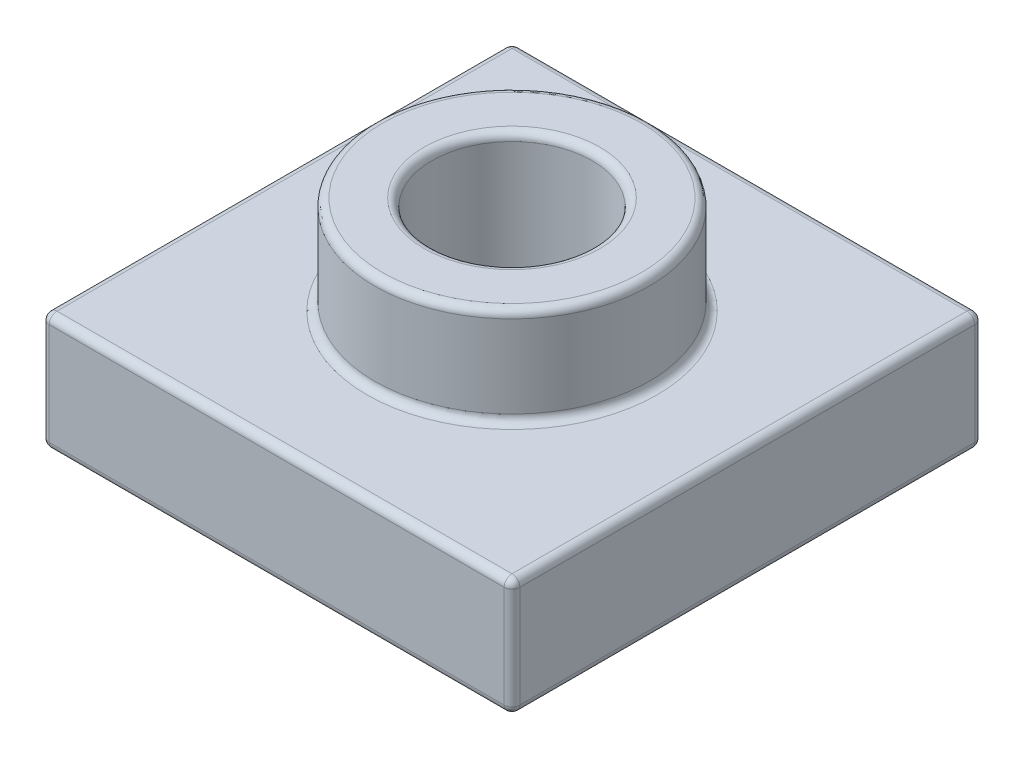
SolidWorks part; units mm, degrees
ref_plane "Front" through (0, 0, 0) normal (0, 0, 1) x (1, 0, 0)
ref_plane "Top" through (0, 0, 0) normal (0, 1, 0) x (1, 0, 0)
ref_plane "Right" through (0, 0, 0) normal (1, 0, 0) x (0, 0, -1)
sketch "Sketch1" plane through (0, 0, 0) normal (0, 1, 0) x (1, 0, 0)
  line L1 (-60, 60) -> (60, 60)
  line L2 (-60, 60) -> (-60, -60)
  line L3 (-60, -60) -> (60, -60)
  line L4 (60, 60) -> (60, -60)
  line L5 (-60, 60) -> (60, -60) construction
  line L6 (-60, -60) -> (60, 60) construction
  point P0 (0, 0)
  dimension "D1" = 120
  dimension "D2" = 120
extrude "Boss-Extrude1" add sketch "Sketch1" along normal blind 30
sketch "Sketch2" plane through (0, 30, 0) normal (0, 1, 0) x (1, 0, 0)
  circle A0 centre (0, 0) radius 35
  dimension "D1" = 70
extrude "Boss-Extrude2" add sketch "Sketch2" along normal blind 25
sketch "Sketch3" plane through (0, 55, 0) normal (0, 1, 0) x (1, 0, 0)
  circle A0 centre (0, 0) radius 20.4252
extrude "Cut-Extrude1" cut sketch "Sketch3" against normal through all
fillet "Fillet10" radius 2 16 edges at (0, 0, -60) (-60, 0, 0) (0, 0, 60) (60, 0, 0) (0, 0, 20.4252) (0, 55, 35) (0, 55, 20.4252) (0, 30, -60) (0, 30, 60) (60, 30, 0) (60, 15, -60) (60, 15, 60) (0, 30, 35) (-60, 30, 0) (-60, 15, -60) (-60, 15, 60)
shell "Shell1" thickness 2 removed face at (0, 0, 0)
